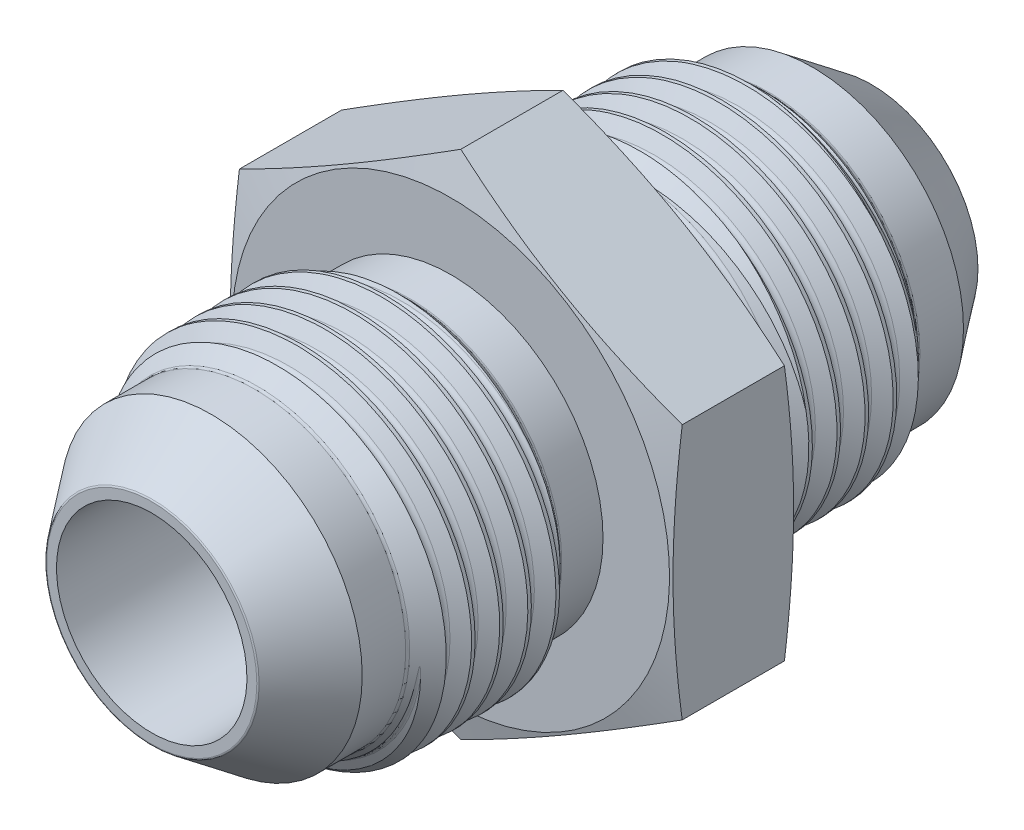
SolidWorks part; units mm, degrees
ref_plane "Front Plane" through (0, 0, 0) normal (0, 0, 1) x (1, 0, 0)
ref_plane "Top Plane" through (0, 0, 0) normal (0, 1, 0) x (1, 0, 0)
ref_plane "Right Plane" through (0, 0, 0) normal (1, 0, 0) x (0, 0, -1)
sketch "Sketch0" plane through (0, 0, 0) normal (1, 0, 0) x (0, 0, -1)
  line L0 (-23.241, 0) -> (0, 0) construction
  line L1 (0, 0) -> (23.241, 0) construction
  line L2 (-16.4846, 11.1125) -> (-16.4846, -11.1125) construction
  line L3 (-23.241, 6.1468) -> (-23.241, -6.1468) construction
  line L4 (-23.241, 6.8453) -> (-23.241, -6.8453) construction
  line L5 (-19.3984, 9.7409) -> (-19.3984, -9.7409) construction
  line L6 (-23.241, 6.8453) -> (-19.3984, 9.7409) construction
  line L7 (-19.3984, 9.7409) -> (-16.4846, 9.7409) construction
  line L8 (-16.4846, 9.7409) -> (-16.4846, -9.7409) construction
  line L9 (-3.9878, 14.2875) -> (-3.9878, -14.2875) construction
  line L10 (-3.9878, 14.1097) -> (-3.9878, -14.1097) construction
  line L11 (-16.4846, 9.7409) -> (-16.4846, 11.1125) construction
  line L12 (-16.4846, 11.1125) -> (-6.7056, 11.1125) construction
  line L13 (-6.7056, 11.1125) -> (-6.7056, 9.8171) construction
  line L14 (-6.7056, 9.8171) -> (-3.9878, 9.8171) construction
  line L15 (-6.7056, 9.8171) -> (-6.7056, -9.8171) construction
  line L16 (-3.9878, 0) -> (-4.191, 0) construction
  point P8 (-3.9878, 0)
  point P13 (-19.3984, 0)
  point P14 (-16.4846, 0)
  point P24 (-6.7056, 0)
  point P26 (-3.937, 0)
  point P27 (3.937, 0)
  dimension "37" = 37
sketch "Sketch1" plane through (0, 0, 0) normal (1, 0, 0) x (0, 0, -1)
  line L0 (-23.241, 0) -> (0, 0)
  line L1 (-23.241, 0) -> (-23.241, 6.782)
  line L2 (-23.1904, 6.8834) -> (-19.3984, 9.7409)
  line L3 (-19.3984, 9.7409) -> (-16.5898, 9.7409)
  line L4 (-16.4102, 9.8153) -> (-15.113, 11.1125)
  line L5 (-15.113, 11.1125) -> (-8.001, 11.1125)
  line L6 (-8.001, 11.1125) -> (-6.78, 9.8915)
  line L7 (-6.6004, 9.8171) -> (0, 9.8171)
  line L8 (0, 9.8171) -> (0, 0)
  line L10 (-16.4846, 11.1125) -> (-16.4846, -11.1125) construction
  line L11 (-19.812, 0) -> (0, 0) construction
  line L12 (-23.241, 6.1468) -> (-23.241, -6.1468) construction
  line L13 (-16.4846, 11.1125) -> (-6.7056, 11.1125) construction
  line L15 (-6.7056, 11.1125) -> (-6.7056, 9.8171) construction
  arc A0 (-23.241, 6.782) -> (-23.1904, 6.8834) centre (-23.114, 6.782) cw
  arc A1 (-16.5898, 9.7409) -> (-16.4102, 9.8153) centre (-16.5898, 9.9949) ccw
  arc A2 (-6.78, 9.8915) -> (-6.6004, 9.8171) centre (-6.6004, 10.0711) ccw
  point P27 (-23.241, 6.8453)
  point P30 (-16.4846, 9.7409)
  point P33 (-6.7056, 9.8171)
  dimension "D1" = 0.127
  dimension "D2" = 0.254
  dimension "D3" = 45
  dimension "D4" = 45
revolve "Revolve1" add sketch "Sketch1" angle 360 about L11
sketch "Sketch2" plane through (0, 0, 23.241) normal (0, 0, 1) x (1, 0, 0)
  circle A0 centre (0, 0) radius 11.1125
  point P3 (0, 11.1125)
curve "Helix/Spiral1" pitch 1.8143 height 21.0675 radius 11.1125 centre (0, 0, 23.241) axis (0, 0, -1) start towards (0, 1, 0) parameters "Pitch"=1.8143
sketch "Sketch3" plane through (0, 0, 0) normal (1, 0, 0) x (0, 0, -1)
  line L0 (-24.9419, 11.3089) -> (-24.0348, 9.7377) construction
  line L1 (-24.0348, 9.7377) -> (-23.1276, 11.3089) construction
  line L2 (-23.1276, 11.3089) -> (-24.9419, 11.3089) construction
  line L3 (-23.241, 11.1125) -> (-24.8285, 11.1125) construction
  line L4 (-24.0348, 11.3089) -> (-24.0348, 11.1125) construction
  line L5 (-24.2237, 10.065) -> (-23.8458, 10.065) construction
  line L6 (-24.0348, 10.065) -> (-24.0348, 9.7377) construction
  line L7 (-24.8852, 11.2107) -> (-24.3182, 10.2287)
  line L8 (-24.8852, 11.2107) -> (-23.1843, 11.2107)
  line L9 (-23.1843, 11.2107) -> (-23.7513, 10.2287)
  line L10 (-24.0348, 9.7377) -> (-24.0348, -11.1125) construction
  line L11 (-24.0348, -11.1125) -> (-22.2205, -11.1125) construction
  line L12 (-22.2205, -11.1125) -> (-20.4062, -11.1125) construction
  line L13 (-20.4062, -11.1125) -> (-18.5919, -11.1125) construction
  line L14 (-18.5919, -11.1125) -> (-16.7776, -11.1125) construction
  line L15 (-16.7776, -11.1125) -> (-14.9633, -11.1125) construction
  line L16 (-14.9633, -11.1125) -> (-13.149, -11.1125) construction
  line L17 (-13.149, -11.1125) -> (-11.3347, -11.1125) construction
  line L21 (-15.113, -11.1125) -> (-8.001, -11.1125) construction
  arc A0 (-24.3182, 10.2287) -> (-23.7513, 10.2287) centre (-24.0348, 10.3924) ccw
  point P13 (-24.0348, 11.2107)
sweep "Cut-Sweep1" cut profiles "Sketch3" path "Helix/Spiral1" align with end faces yes
ref_axis "Axis1" through (-10.4775, 0, 0) along (1, 0, 0)
pattern_circular "CirPattern1" count 2 over 180 about axis through (-10.4775, 0, 0) along (1, 0, 0) reverse direction yes of bodies 103
sketch "Sketch4" plane through (0, 0, 0) normal (0, 0, 1) x (1, 0, 0)
  line L1 (0, 16.4978) -> (-14.2875, 8.2489)
  line L2 (-14.2875, 8.2489) -> (-14.2875, -8.2489)
  line L3 (-14.2875, -8.2489) -> (0, -16.4978)
  line L4 (0, -16.4978) -> (14.2875, -8.2489)
  line L5 (14.2875, -8.2489) -> (14.2875, 8.2489)
  line L6 (14.2875, 8.2489) -> (0, 16.4978)
  circle A0 centre (0, 0) radius 14.2875 construction
extrude "Boss-Extrude1" add sketch "Sketch4" along normal up to vertex (3.937 mm away) and the other way up to vertex (3.937 mm away) up to point (0, 0, 3.937) other way up to point (0, 0, -3.937)
sketch "Sketch5" plane through (0, 0, 0) normal (1, 0, 0) x (0, 0, -1)
  line L0 (-3.937, 18.8859) -> (3.937, 18.8859)
  line L1 (-3.937, 18.8859) -> (-3.937, 14.1097)
  line L2 (-3.937, 14.1097) -> (-3.2971, 16.4978)
  line L3 (-3.2971, 16.4978) -> (3.2971, 16.4978)
  line L4 (3.2971, 16.4978) -> (3.937, 14.1097)
  line L5 (3.937, 14.1097) -> (3.937, 18.8859)
  line L7 (-3.937, 16.4978) -> (3.937, 16.4978) construction
  line L8 (-3.9878, 0) -> (0, 0) construction
  dimension "D1" = 15
revolve "Cut-Revolve1" cut sketch "Sketch5" angle 360 about L8
sketch "Sketch6" plane through (0, 0, 0) normal (1, 0, 0) x (0, 0, -1)
  line L0 (-23.241, 6.1468) -> (0, 6.1468)
  line L1 (6.1468, 0) -> (-23.241, 0)
  line L2 (-23.241, 0) -> (-23.241, 6.1468)
  arc A0 (0, 6.1468) -> (6.1468, 0) centre (0, 0) cw
revolve "Cut-Revolve2" cut sketch "Sketch6" angle 360 about L1
pattern_circular "CirPattern2" count 2 over 180 about axis through (-10.4775, 0, 0) along (1, 0, 0) of "Cut-Revolve2" reverse direction yes
equation "\"D3@Helix/Spiral1\" = \"Pitch@Helix/Spiral1\" + \"J@Sketch0\""
equation "\"P@Sketch3\" = \"Pitch@Helix/Spiral1\""
equation "\"H/8@Sketch3\" = \"H@Sketch3\" / 8"
equation "\"2/3H@Sketch3\" = 2/3 * \"H@Sketch3\""
